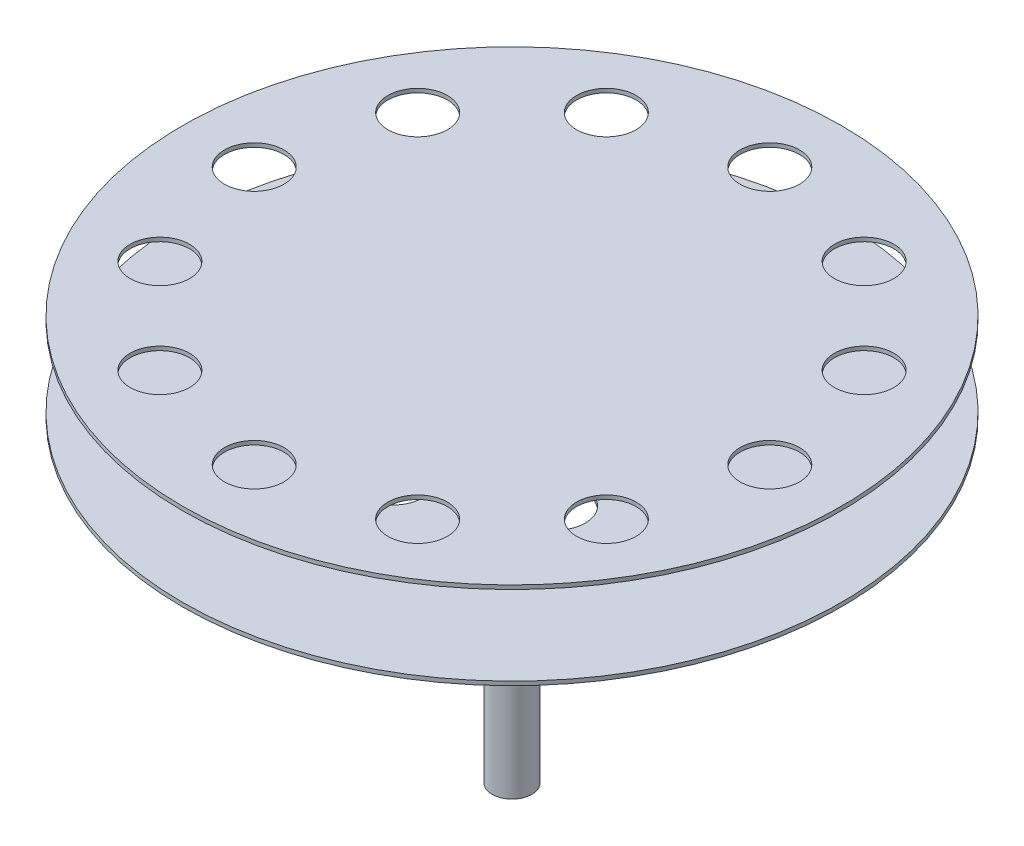
SolidWorks part; units mm, degrees
ref_plane "Front Plane" through (0, 0, 0) normal (0, 0, 1) x (1, 0, 0)
ref_plane "Top Plane" through (0, 0, 0) normal (0, 1, 0) x (1, 0, 0)
ref_plane "Right Plane" through (0, 0, 0) normal (1, 0, 0) x (0, 0, -1)
sketch "Sketch1" plane through (0, 0, 0) normal (0, 0, 1) x (1, 0, 0)
  line L0 (0, 0) -> (0, 52.2611) construction
  line L1 (0, 102) -> (-83.0999, 102)
  line L2 (-83.0999, 102) -> (-83.0999, 101)
  line L3 (-83.0999, 101) -> (-5, 101)
  line L4 (-5, 101) -> (-5, 81)
  line L5 (-5, 81) -> (-83.0999, 81)
  line L6 (-83.0999, 81) -> (-83.0999, 80)
  line L7 (-83.0999, 80) -> (-5, 80)
  line L8 (-5, 80) -> (-5, 0)
  line L9 (-5, 0) -> (0, 0)
  line L10 (0, 0) -> (0, 102)
  line L11 (-5, 81) -> (-5, 80) construction
  line L12 (-83.0999, 101) -> (-83.0999, 81) construction
  dimension "D1" = 83.0999
  dimension "D2" = 1
  dimension "D3" = 20
  dimension "D4" = 5
  dimension "D5" = 80
ref_axis "Axis1" through (0, 54.8742, 0) along (0, -1, 0)
revolve "Revolve1" add sketch "Sketch1" angle 360 about axis through (0, 54.8742, 0) along (0, -1, 0)
sketch "Sketch2" plane through (0, 102, 0) normal (0, 1, 0) x (1, 0, 0)
  line L0 (0, 0) -> (0, 65) construction
  circle A0 centre (0, 65) radius 7.5
  dimension "D1" = 15
  dimension "D2" = 65
extrude "Cut-Extrude1" cut sketch "Sketch2" against normal blind 2
pattern_circular "CirPattern1" count 12 over 360 about axis through (0, 54.8742, 0) along (0, -1, 0) of "Cut-Extrude1"
sketch "Sketch3" plane through (0, 80, 0) normal (0, -1, 0) x (1, 0, 0)
  line L0 (0, 0) -> (0, 30) construction
  circle A0 centre (0, 30) radius 7.5
  dimension "D2" = 15
  dimension "D1" = 30
extrude "Cut-Extrude2" cut sketch "Sketch3" against normal blind 2
pattern_circular "CirPattern2" count 6 over 360 about axis through (0, 54.8742, 0) along (0, -1, 0) of "Cut-Extrude2"
equation "\"TubeDiameter\" = 6.5433in"
equation "\"D1@Sketch1\"=\"TubeDiameter\"/2"
